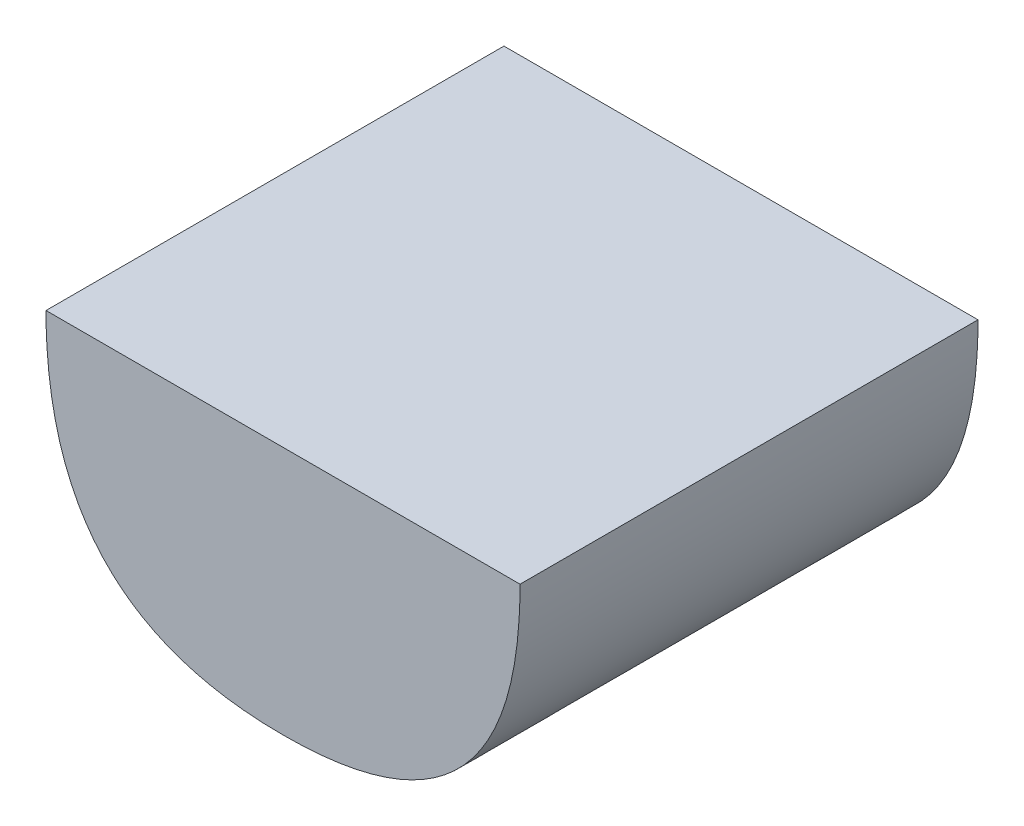
SolidWorks part; units mm, degrees
ref_plane "Front Plane" through (0, 0, 0) normal (0, 0, 1) x (1, 0, 0)
ref_plane "Top Plane" through (0, 0, 0) normal (0, 1, 0) x (1, 0, 0)
ref_plane "Right Plane" through (0, 0, 0) normal (1, 0, 0) x (0, 0, -1)
sketch "Sketch1" plane through (0, 0, 0) normal (0, 0, 1) x (1, 0, 0)
  line L0 (0, 0) -> (0, 317.813) construction
  line L2 (-302.357, 317.813) -> (302.357, 317.813)
  conic Q0 (0, 0) -> (302.357, 317.813) control (302.357, -0.0664) rho 0.504796
  conic Q1 (0, 0) -> (-302.357, 317.813) control (-302.357, -0.0664) rho 0.504796
extrude "Boss-Extrude1" add sketch "Sketch1" against normal blind 584.2 contours L2 Q0 Q1
